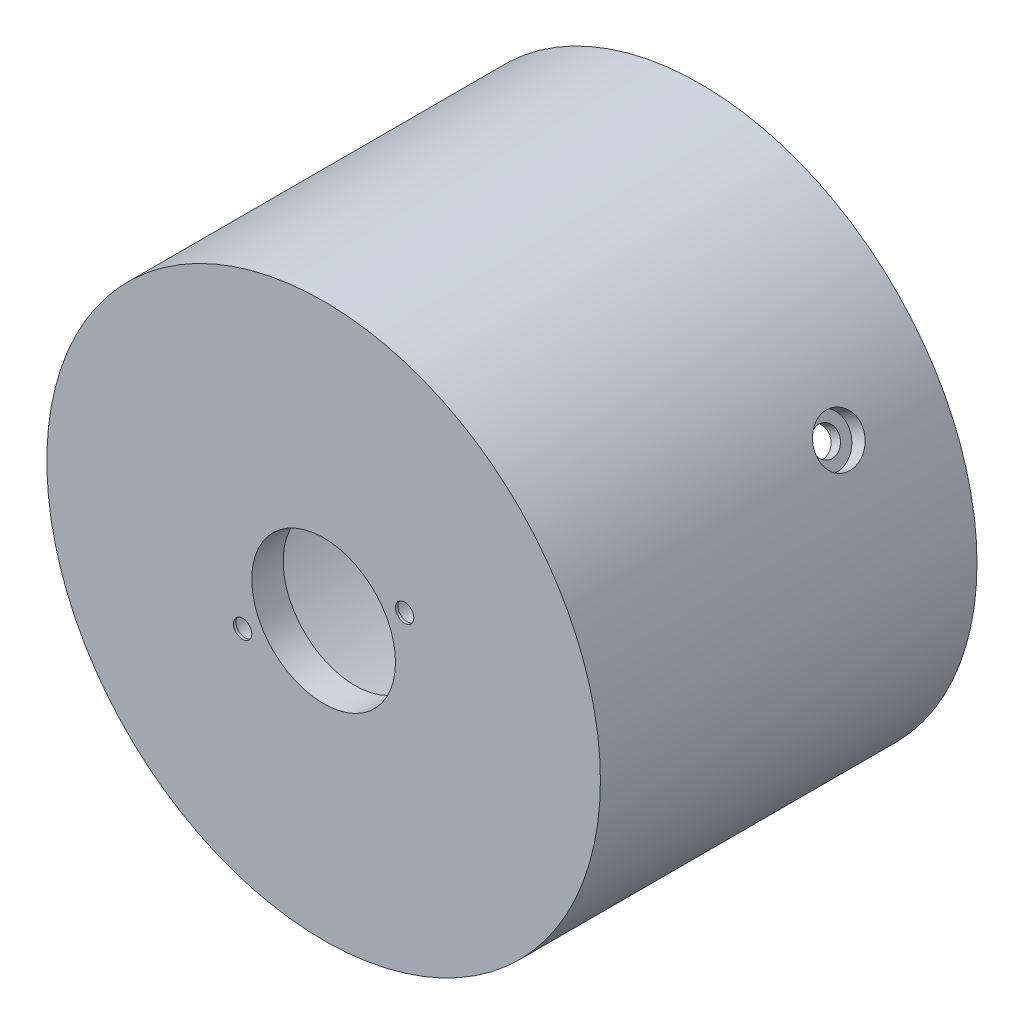
SolidWorks part; units mm, degrees
material "Acrylic (Medium-high impact)"
ref_plane "Front Plane" through (0, 0, 0) normal (0, 0, 1) x (1, 0, 0)
ref_plane "Top Plane" through (0, 0, 0) normal (0, 1, 0) x (1, 0, 0)
ref_plane "Right Plane" through (0, 0, 0) normal (1, 0, 0) x (0, 0, -1)
sketch "Sketch1" plane through (0, 0, 0) normal (0, 0, 1) x (1, 0, 0)
  circle A0 centre (0, 0) radius 25.3365
  circle A1 centre (0, 0) radius 28.0035
  dimension "D1" = 50.673
extrude "Boss-Extrude1" add sketch "Sketch1" along normal blind 38.1
sketch "Sketch10" plane through (0, 0, 38.1) normal (0, 0, 1) x (1, 0, 0)
  circle A0 centre (0, 0) radius 28.0035
  circle A1 centre (0, 0) radius 28.0035 construction
extrude "Boss-Extrude2" add sketch "Sketch10" against normal blind 3.175
ref_plane "Plane1" through (0, 0, 10.2108) normal (0, 0, -1) x (-1, 0, 0)
sketch "Sketch11" plane through (0, 0, 10.2108) normal (0, 0, -1) x (-1, 0, 0)
  line L0 (0, 0) -> (0, -28.0035) construction
  line L1 (0, 0) -> (-24.2517, 14.0018) construction
  line L2 (0, 0) -> (24.2517, 14.0018) construction
  circle A0 centre (0, 0) radius 28.0035 construction
  dimension "D1" = 120
ref_plane "Plane2" through (-24.2517, 14.0018, 10.2108) normal (-0.866, 0.5, 0) x (0, 0, -1)
ref_plane "Plane3" through (24.2517, 14.0018, 10.2108) normal (0.866, 0.5, 0) x (0, 0, 1)
ref_plane "Plane4" through (0, -28.0035, 10.2108) normal (0, -1, 0) x (-1, 0, 0)
hole_wizard "CBORE for #2 Pan Head Machine Screw1" positions "Sketch15" profile "Sketch14" counterbore size "#2" standard "ANSI Inch" end condition up to next
sketch "Sketch15" plane through (-24.2517, 14.0018, 10.2108) normal (-0.866, 0.5, 0) x (0, 0, -1)
  point P0 (0, 0)
sketch "Sketch14" plane through (-24.2517, 14.0018, 10.2108) normal (0, 0, 1) x (-0.5, -0.866, 0)
  line L0 (0, 0) -> (0, 2.667)
  line L1 (0, 2.667) -> (1.3526, 2.667)
  line L3 (1.3526, 2.667) -> (1.3525, 1.5748)
  line L4 (1.3525, 1.5748) -> (2.3812, 1.5748)
  line L5 (2.3812, 1.5748) -> (2.3812, 0)
  line L7 (2.3812, 0) -> (0, 0)
  line L11 (0, -6.35) -> (0, 107.95) construction
  dimension "Thru Hole Dia." = 2.7051
  dimension "Thru Hole Depth" = 2.667
  dimension "C'Bore Dia." = 4.7625
  dimension "C'Bore Depth" = 1.5748
hole_wizard "CBORE for #2 Pan Head Machine Screw2" positions "Sketch17" profile "Sketch16" counterbore size "#2" standard "ANSI Inch" end condition up to next
sketch "Sketch17" plane through (24.2517, 14.0018, 10.2108) normal (0.866, 0.5, 0) x (0, 0, 1)
  point P0 (0, 0)
sketch "Sketch16" plane through (24.2517, 14.0018, 10.2108) normal (0, 0, 1) x (-0.5, 0.866, 0)
  line L0 (0, 0) -> (0, 2.667)
  line L1 (0, 2.667) -> (1.3526, 2.667)
  line L3 (1.3526, 2.667) -> (1.3526, 1.5748)
  line L4 (1.3526, 1.5748) -> (2.3812, 1.5748)
  line L5 (2.3812, 1.5748) -> (2.3812, 0)
  line L7 (2.3812, 0) -> (0, 0)
  line L11 (0, -6.35) -> (0, 107.95) construction
  dimension "Thru Hole Dia." = 2.7051
  dimension "Thru Hole Depth" = 2.667
  dimension "C'Bore Dia." = 4.7625
  dimension "C'Bore Depth" = 1.5748
hole_wizard "CBORE for #2 Pan Head Machine Screw3" positions "Sketch19" profile "Sketch18" counterbore size "#2" standard "ANSI Inch" end condition up to next
sketch "Sketch19" plane through (0, -28.0035, 10.2108) normal (0, -1, 0) x (-1, 0, 0)
  point P0 (0, 0)
sketch "Sketch18" plane through (0, -28.0035, 10.2108) normal (1, 0, 0) x (0, 0, -1)
  line L0 (0, 0) -> (0, 2.667)
  line L1 (0, 2.667) -> (1.3526, 2.667)
  line L3 (1.3526, 2.667) -> (1.3526, 1.5748)
  line L4 (1.3526, 1.5748) -> (2.3812, 1.5748)
  line L5 (2.3812, 1.5748) -> (2.3812, 0)
  line L7 (2.3812, 0) -> (0, 0)
  line L11 (0, -6.35) -> (0, 107.95) construction
  dimension "Thru Hole Dia." = 2.7051
  dimension "Thru Hole Depth" = 2.667
  dimension "C'Bore Dia." = 4.7625
  dimension "C'Bore Depth" = 1.5748
sketch "Sketch20" plane through (0, 0, 38.1) normal (0, 0, 1) x (1, 0, 0)
  circle A0 centre (0, 0) radius 7.27
  circle A1 centre (0, 0) radius 6 construction
  dimension "D1" = 1.27
extrude "Cut-Extrude1" cut sketch "Sketch20" against normal up to next
hole_wizard "Hole1" positions "Sketch21" profile "Sketch22" legacy
sketch "Sketch21" plane through (0, 0, 34.925) normal (0, 0, -1) x (-1, 0, 0)
  point P0 (-8.1957, 4.8042)
  point P3 (8.1957, -4.8042)
sketch "Sketch22" plane through (8.1957, 4.8042, 34.925) normal (1, 0, 0) x (0, 1, 0)
  line L0 (0, 0) -> (0, 2.921)
  line L1 (0, 2.921) -> (1.4986, 2.921)
  line L2 (1.4986, 2.921) -> (1.6383, 0)
  line L3 (1.6383, 0) -> (0, 0)
  line L4 (0, 110) -> (0, -10) construction
  dimension "Minor Diameter" = 2.9972
  dimension "Depth" = 2.921
  dimension "Major Diameter" = 3.2766
hole_wizard "#0 Clearance Hole1" positions "Sketch23" profile "Sketch24" hole size "#0" standard "ANSI Inch" end condition up to next
sketch "Sketch23" plane through (0, 0, 34.925) normal (0, 0, -1) x (-1, 0, 0)
  point P0 (-8.1957, 4.8042)
  point P3 (8.1957, -4.8042)
sketch "Sketch24" plane through (8.1957, 4.8042, 34.925) normal (1, 0, 0) x (0, 1, 0)
  line L0 (0, 0) -> (0, 3.175)
  line L1 (0, 3.175) -> (0.9271, 3.175)
  line L2 (0.9271, 3.175) -> (0.9271, 0)
  line L5 (0.9271, 0) -> (0, 0)
  line L11 (0, -6.35) -> (0, 107.95) construction
  dimension "Thru Hole Dia." = 1.8542
  dimension "Thru Hole Depth" = 3.175
chamfer "Chamfer1" distance 1.27 angle 45 1 edges at (25.3365, 0, 0)
